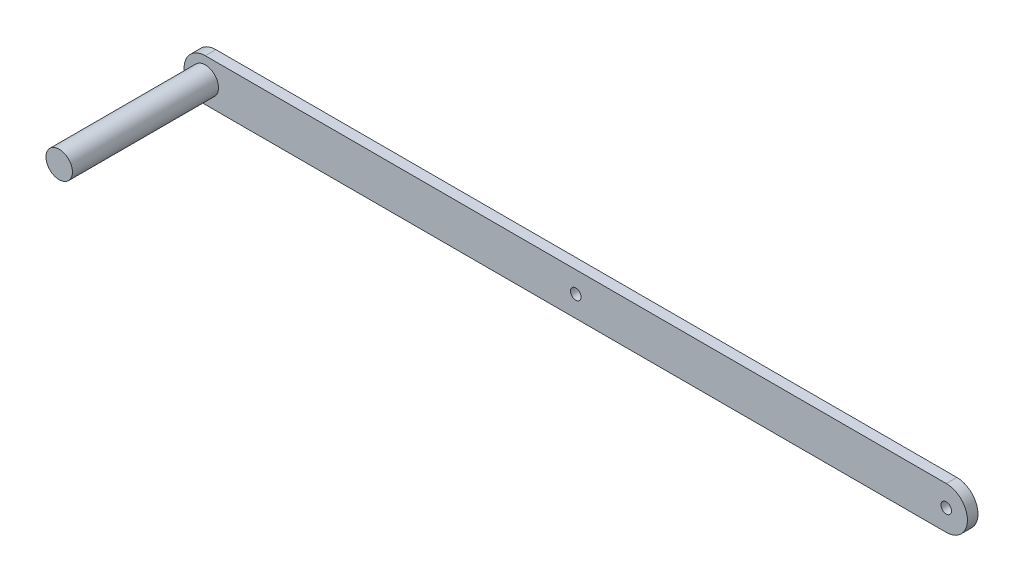
SolidWorks part; units mm, degrees
ref_plane "Ön Düzlem" through (0, 0, 0) normal (0, 0, 1) x (1, 0, 0)
ref_plane "Üst Düzlem" through (0, 0, 0) normal (0, 1, 0) x (1, 0, 0)
ref_plane "Sağ Düzlem" through (0, 0, 0) normal (1, 0, 0) x (0, 0, -1)
sketch "Çizim1" plane through (0, 0, 0) normal (0, 0, 1) x (1, 0, 0)
  line L0 (-350, 0) -> (350, 0) construction
  line L1 (-350, 20) -> (350, 20)
  line L2 (-350, -20) -> (350, -20)
  arc A0 (-350, 20) -> (-350, -20) centre (-350, 0) ccw
  arc A1 (350, -20) -> (350, 20) centre (350, 0) ccw
  circle A2 centre (350, 0) radius 5
  circle A3 centre (-350, 0) radius 12.5
  point P2 (0, 0)
  dimension "D2" = 10
  dimension "D3" = 20
  dimension "D4" = 25
  dimension "D1" = 700
extrude "Yükseklik-Ekstrüzyon1" add sketch "Çizim1" along normal mid plane 10
sketch "Çizim2" plane through (0, 0, 5) normal (0, 0, 1) x (1, 0, 0)
  circle A0 centre (0, 0) radius 5
  point P3 (0, 0)
  dimension "D1" = 10
extrude "Kes-Ekstrüzyon1" cut sketch "Çizim2" against normal blind 15 contours A0
extrude "Yükseklik-Ekstrüzyon2" add sketch "Çizim1<3>" along normal blind 143 contours A3 region at (-350, 0, 0)
sketch "Çizim1<3>" plane through (0, 0, 0) normal (0, 0, 1) x (1, 0, 0) same geometry as "Çizim1"
